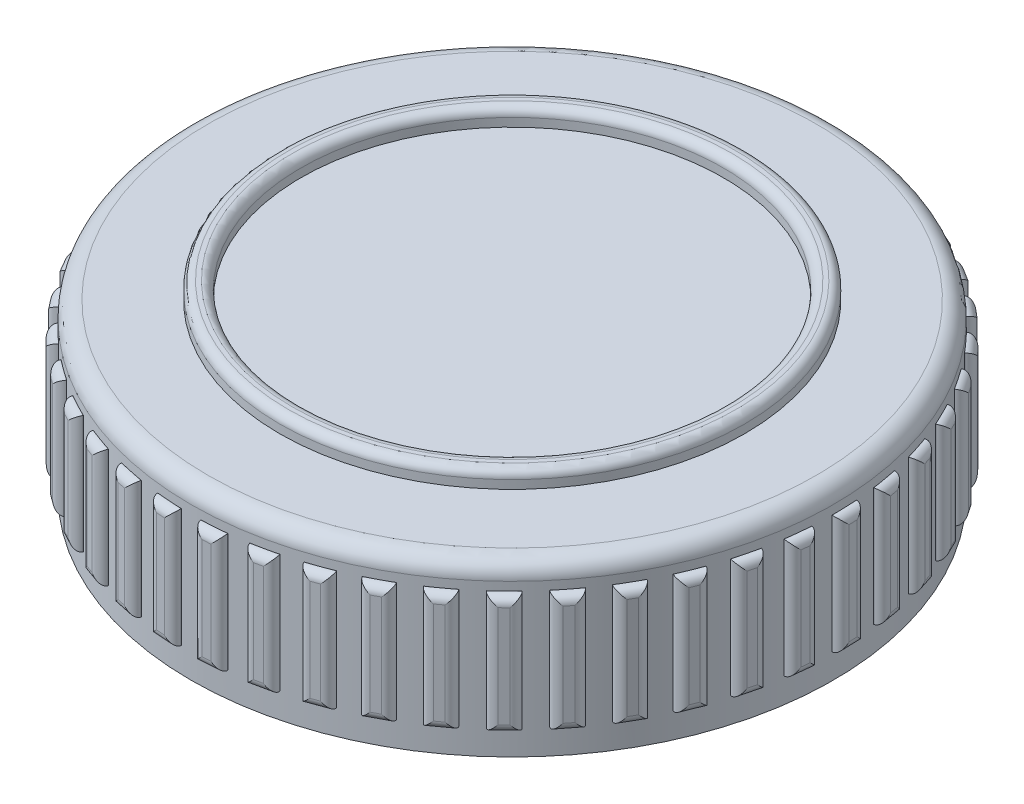
SolidWorks part; units mm, degrees
ref_plane "Front Plane" through (0, 0, 0) normal (0, 0, 1) x (1, 0, 0)
ref_plane "Top Plane" through (0, 0, 0) normal (0, 1, 0) x (1, 0, 0)
ref_plane "Right Plane" through (0, 0, 0) normal (1, 0, 0) x (0, 0, -1)
sketch "Sketch1" plane through (0, 0, 0) normal (0, 1, 0) x (1, 0, 0)
  circle A0 centre (0, 0) radius 38
  dimension "D1" = 76
extrude "Boss-Extrude1" add sketch "Sketch1" along normal blind 20
shell "Shell1" thickness 3 removed face at (0, 0, 38)
sketch "Sketch2" plane through (0, 0, 0) normal (0, 1, 0) x (1, 0, 0)
  circle A0 centre (0, 0) radius 27.5
  circle A1 centre (0, 0) radius 25
  dimension "D1" = 55
  dimension "D2" = 50
extrude "Boss-Extrude2" add sketch "Sketch2" along normal blind 2 from surface starting at face at (0, 20, 38)
sketch "Sketch4" plane through (0, 0, 0) normal (0, 1, 0) x (1, 0, 0)
  line L0 (-1.5, 37.9147) -> (-1.5, 39)
  line L1 (-1.5, -39) -> (1.5, -39) construction
  line L2 (-1.5, -39) -> (-1.5, 39) construction
  line L3 (-1.5, 39) -> (1.5, 39) construction
  line L4 (1.5, -39) -> (1.5, 39) construction
  line L5 (-1.5, -39) -> (1.5, 39) construction
  line L6 (-1.5, 39) -> (1.5, -39) construction
  line L7 (-1.5, 39) -> (1.5, 39)
  line L8 (1.5, 39) -> (1.5, 37.9147)
  line L9 (1.5, 37.9147) -> (-1.5, 37.9147)
  point P0 (0, 0)
  dimension "D1" = 3
  dimension "D2" = 78
  dimension "D3" = 1.0853
extrude "Boss-Extrude3" add sketch "Sketch4" along normal blind 14 from offset 3
fillet "Fillet1" radius 1 4 edges at (1.5, 10, -39) (0, 17, -39) (-1.5, 10, -39) (0, 3, -39)
pattern_circular "CirPattern2" count 45 over 360 about axis through (0, 20, 0) along (0, 1, 0) of "Fillet1", "Boss-Extrude3"
fillet "Fillet2" radius 1 2 edges at (0, 22, 25) (0, 22, 27.5)
fillet "Fillet3" radius 2 1 edges at (0, 20, 38)
